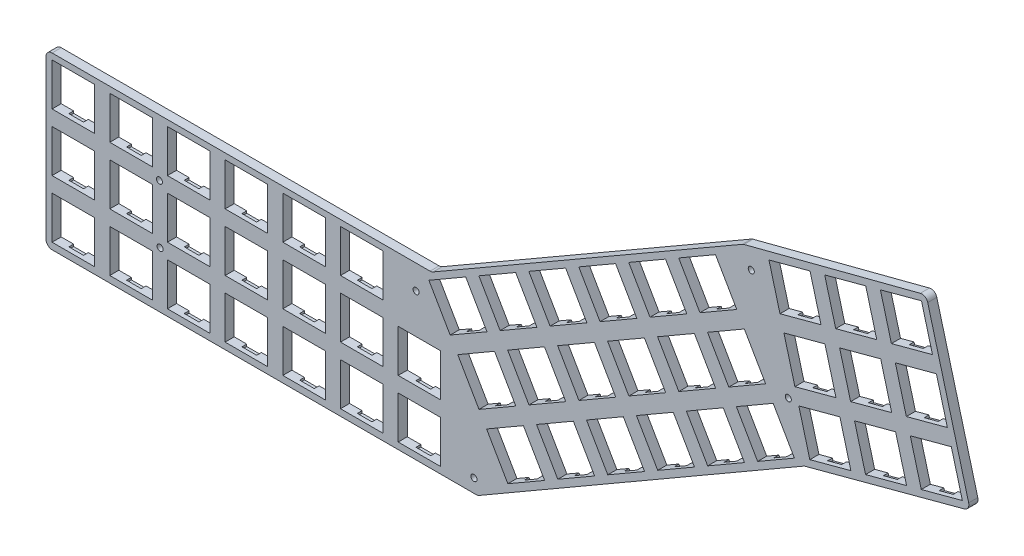
SolidWorks part; units mm, degrees
ref_plane "Plan de face" through (0, 0, 0) normal (0, 0, 1) x (1, 0, 0)
ref_plane "Plan de dessus" through (0, 0, 0) normal (0, 1, 0) x (1, 0, 0)
ref_plane "Plan de droite" through (0, 0, 0) normal (1, 0, 0) x (0, 0, -1)
sketch "Model" plane through (0, 0, 0) normal (0, 0, 1) x (1, 0, 0)
  line L0 (-149.6088, -15.6876) -> (-135.6088, -15.6876) construction
  line L1 (-149.6088, 3.3124) -> (-135.6088, 3.3124) construction
  line L2 (-149.6088, 3.3124) -> (-149.6088, -10.6876) construction
  line L3 (-149.6088, -10.6876) -> (-135.6088, -10.6876) construction
  line L4 (-135.6088, 3.3124) -> (-135.6088, -10.6876) construction
  line L5 (-149.6088, -15.6876) -> (-149.6088, -29.6876) construction
  line L6 (-149.6088, -29.6876) -> (-135.6088, -29.6876) construction
  line L7 (-135.6088, -15.6876) -> (-135.6088, -29.6876) construction
  line L8 (-149.6088, -34.6876) -> (-135.6088, -34.6876) construction
  line L9 (-149.6088, -34.6876) -> (-149.6088, -48.6876) construction
  line L10 (-149.6088, -48.6876) -> (-135.6088, -48.6876) construction
  line L11 (-135.6088, -34.6876) -> (-135.6088, -48.6876) construction
  line L12 (-149.6088, 3.3124) -> (-149.6088, -15.6876) construction
  line L13 (-130.6088, -15.6876) -> (-116.6088, -15.6876) construction
  line L14 (-130.6088, 3.3124) -> (-116.6088, 3.3124) construction
  line L15 (-130.6088, 3.3124) -> (-130.6088, -10.6876) construction
  line L16 (-130.6088, -10.6876) -> (-116.6088, -10.6876) construction
  line L17 (-116.6088, 3.3124) -> (-116.6088, -10.6876) construction
  line L18 (-130.6088, -15.6876) -> (-130.6088, -29.6876) construction
  line L19 (-130.6088, -29.6876) -> (-116.6088, -29.6876) construction
  line L20 (-116.6088, -15.6876) -> (-116.6088, -29.6876) construction
  line L21 (-130.6088, -34.6876) -> (-116.6088, -34.6876) construction
  line L22 (-130.6088, -34.6876) -> (-130.6088, -48.6876) construction
  line L23 (-130.6088, -48.6876) -> (-116.6088, -48.6876) construction
  line L24 (-116.6088, -34.6876) -> (-116.6088, -48.6876) construction
  line L25 (-130.6088, 3.3124) -> (-130.6088, -15.6876) construction
  line L26 (-111.6088, -15.6876) -> (-97.6088, -15.6876) construction
  line L27 (-111.6088, 3.3124) -> (-97.6088, 3.3124) construction
  line L28 (-111.6088, 3.3124) -> (-111.6088, -10.6876) construction
  line L29 (-111.6088, -10.6876) -> (-97.6088, -10.6876) construction
  line L30 (-97.6088, 3.3124) -> (-97.6088, -10.6876) construction
  line L31 (-111.6088, -15.6876) -> (-111.6088, -29.6876) construction
  line L32 (-111.6088, -29.6876) -> (-97.6088, -29.6876) construction
  line L33 (-97.6088, -15.6876) -> (-97.6088, -29.6876) construction
  line L34 (-111.6088, -34.6876) -> (-97.6088, -34.6876) construction
  line L35 (-111.6088, -34.6876) -> (-111.6088, -48.6876) construction
  line L36 (-111.6088, -48.6876) -> (-97.6088, -48.6876) construction
  line L37 (-97.6088, -34.6876) -> (-97.6088, -48.6876) construction
  line L38 (-111.6088, 3.3124) -> (-111.6088, -15.6876) construction
  line L39 (-92.6088, -15.6876) -> (-78.6088, -15.6876) construction
  line L40 (-92.6088, 3.3124) -> (-78.6088, 3.3124) construction
  line L41 (-92.6088, 3.3124) -> (-92.6088, -10.6876) construction
  line L42 (-92.6088, -10.6876) -> (-78.6088, -10.6876) construction
  line L43 (-78.6088, 3.3124) -> (-78.6088, -10.6876) construction
  line L44 (-92.6088, -15.6876) -> (-92.6088, -29.6876) construction
  line L45 (-92.6088, -29.6876) -> (-78.6088, -29.6876) construction
  line L46 (-78.6088, -15.6876) -> (-78.6088, -29.6876) construction
  line L47 (-92.6088, -34.6876) -> (-78.6088, -34.6876) construction
  line L48 (-92.6088, -34.6876) -> (-92.6088, -48.6876) construction
  line L49 (-92.6088, -48.6876) -> (-78.6088, -48.6876) construction
  line L50 (-78.6088, -34.6876) -> (-78.6088, -48.6876) construction
  line L51 (-92.6088, 3.3124) -> (-92.6088, -15.6876) construction
  line L52 (-73.6088, -15.6876) -> (-59.6088, -15.6876) construction
  line L53 (-73.6088, 3.3124) -> (-59.6088, 3.3124) construction
  line L54 (-73.6088, 3.3124) -> (-73.6088, -10.6876) construction
  line L55 (-73.6088, -10.6876) -> (-59.6088, -10.6876) construction
  line L56 (-59.6088, 3.3124) -> (-59.6088, -10.6876) construction
  line L57 (-73.6088, -15.6876) -> (-73.6088, -29.6876) construction
  line L58 (-73.6088, -29.6876) -> (-59.6088, -29.6876) construction
  line L59 (-59.6088, -15.6876) -> (-59.6088, -29.6876) construction
  line L60 (-73.6088, -34.6876) -> (-59.6088, -34.6876) construction
  line L61 (-73.6088, -34.6876) -> (-73.6088, -48.6876) construction
  line L62 (-73.6088, -48.6876) -> (-59.6088, -48.6876) construction
  line L63 (-59.6088, -34.6876) -> (-59.6088, -48.6876) construction
  line L64 (-73.6088, 3.3124) -> (-73.6088, -15.6876) construction
  line L65 (-54.6088, -15.6876) -> (-40.6088, -15.6876) construction
  line L66 (-54.6088, 3.3124) -> (-40.6088, 3.3124) construction
  line L67 (-54.6088, 3.3124) -> (-54.6088, -10.6876) construction
  line L68 (-54.6088, -10.6876) -> (-40.6088, -10.6876) construction
  line L69 (-40.6088, 3.3124) -> (-40.6088, -10.6876) construction
  line L70 (-54.6088, -15.6876) -> (-54.6088, -29.6876) construction
  line L71 (-54.6088, -29.6876) -> (-40.6088, -29.6876) construction
  line L72 (-40.6088, -15.6876) -> (-40.6088, -29.6876) construction
  line L73 (-54.6088, -34.6876) -> (-40.6088, -34.6876) construction
  line L74 (-54.6088, -34.6876) -> (-54.6088, -48.6876) construction
  line L75 (-54.6088, -48.6876) -> (-40.6088, -48.6876) construction
  line L76 (-40.6088, -34.6876) -> (-40.6088, -48.6876) construction
  line L77 (-54.6088, 3.3124) -> (-54.6088, -15.6876) construction
  line L78 (-35.6088, -15.6876) -> (-21.6088, -15.6876) construction
  line L79 (-35.6088, 3.3124) -> (-21.6088, 3.3124) construction
  line L80 (-35.6088, 3.3124) -> (-35.6088, -10.6876) construction
  line L81 (-35.6088, -10.6876) -> (-21.6088, -10.6876) construction
  line L82 (-21.6088, 3.3124) -> (-21.6088, -10.6876) construction
  line L83 (-35.6088, -15.6876) -> (-35.6088, -29.6876) construction
  line L84 (-35.6088, -29.6876) -> (-21.6088, -29.6876) construction
  line L85 (-21.6088, -15.6876) -> (-21.6088, -29.6876) construction
  line L86 (-35.6088, -34.6876) -> (-21.6088, -34.6876) construction
  line L87 (-35.6088, -34.6876) -> (-35.6088, -48.6876) construction
  line L88 (-35.6088, -48.6876) -> (-21.6088, -48.6876) construction
  line L89 (-21.6088, -34.6876) -> (-21.6088, -48.6876) construction
  line L90 (-35.6088, 3.3124) -> (-35.6088, -15.6876) construction
  line L91 (-149.6088, -15.6876) -> (-130.6088, -15.6876) construction
  line L92 (-19.6088, -13.6876) -> (-18.8669, -14.9725) construction
  line L93 (-37.6088, 5.3124) -> (-19.6088, 5.3124) construction
  line L94 (-19.6088, 5.3124) -> (-19.6088, -12.6876) construction
  line L95 (-37.6088, -12.6876) -> (-19.6088, -12.6876) construction
  line L96 (-37.6088, 5.3124) -> (-37.6088, -12.6876) construction
  line L97 (-56.6088, 5.3124) -> (-38.6088, 5.3124) construction
  line L98 (-38.6088, 5.3124) -> (-38.6088, -12.6876) construction
  line L99 (-56.6088, -12.6876) -> (-38.6088, -12.6876) construction
  line L100 (-56.6088, 5.3124) -> (-56.6088, -12.6876) construction
  line L101 (3.8161, 21.7392) -> (12.8161, 6.1508) construction
  line L102 (12.8161, 6.1508) -> (-2.7723, -2.8492) construction
  line L103 (-11.7723, 12.7392) -> (-2.7723, -2.8492) construction
  line L104 (3.8161, 21.7392) -> (-11.7723, 12.7392) construction
  line L105 (-12.6383, 12.2392) -> (-3.6383, -3.3492) construction
  line L106 (-3.6383, -3.3492) -> (-19.2268, -12.3492) construction
  line L107 (-28.2268, 3.2392) -> (-19.2268, -12.3492) construction
  line L108 (-12.6383, 12.2392) -> (-28.2268, 3.2392) construction
  line L109 (88.6341, 26.8303) -> (73.0456, 17.8303) construction
  line L110 (-13.3704, 9.5072) -> (-3.8704, -6.9473) construction
  line L111 (3.0841, 19.0072) -> (12.5841, 2.5527) construction
  line L112 (19.5386, 28.5072) -> (29.0386, 12.0527) construction
  line L113 (35.9931, 38.0072) -> (45.4931, 21.5527) construction
  line L114 (52.4475, 47.5072) -> (61.9475, 31.0527) construction
  line L115 (68.902, 57.0072) -> (78.402, 40.5527) construction
  line L116 (73.0456, 17.8303) -> (82.0456, 2.2418) construction
  line L117 (-6.4947, -30.4018) -> (0.5053, -42.5261) construction
  line L118 (12.6296, -35.5261) -> (0.5053, -42.5261) construction
  line L119 (5.6296, -23.4018) -> (12.6296, -35.5261) construction
  line L120 (5.6296, -23.4018) -> (-6.4947, -30.4018) construction
  line L121 (-15.9947, -13.9473) -> (-8.9947, -26.0717) construction
  line L122 (3.1296, -19.0717) -> (-8.9947, -26.0717) construction
  line L123 (-3.8704, -6.9473) -> (3.1296, -19.0717) construction
  line L124 (-25.4947, 2.5072) -> (-18.4947, -9.6172) construction
  line L125 (-6.3704, -2.6172) -> (-18.4947, -9.6172) construction
  line L126 (-13.3704, 9.5072) -> (-6.3704, -2.6172) construction
  line L127 (-13.3704, 9.5072) -> (-25.4947, 2.5072) construction
  line L128 (-3.8704, -6.9473) -> (-15.9947, -13.9473) construction
  line L129 (9.9597, -20.9018) -> (16.9597, -33.0261) construction
  line L130 (29.0841, -26.0261) -> (16.9597, -33.0261) construction
  line L131 (22.0841, -13.9018) -> (29.0841, -26.0261) construction
  line L132 (22.0841, -13.9018) -> (9.9597, -20.9018) construction
  line L133 (0.4597, -4.4473) -> (7.4597, -16.5717) construction
  line L134 (19.5841, -9.5717) -> (7.4597, -16.5717) construction
  line L135 (12.5841, 2.5527) -> (19.5841, -9.5717) construction
  line L136 (-9.0403, 12.0072) -> (-2.0403, -0.1172) construction
  line L137 (10.0841, 6.8828) -> (-2.0403, -0.1172) construction
  line L138 (3.0841, 19.0072) -> (10.0841, 6.8828) construction
  line L139 (3.0841, 19.0072) -> (-9.0403, 12.0072) construction
  line L140 (12.5841, 2.5527) -> (0.4597, -4.4473) construction
  line L141 (26.4142, -11.4018) -> (33.4142, -23.5261) construction
  line L142 (45.5386, -16.5261) -> (33.4142, -23.5261) construction
  line L143 (38.5386, -4.4018) -> (45.5386, -16.5261) construction
  line L144 (38.5386, -4.4018) -> (26.4142, -11.4018) construction
  line L145 (16.9142, 5.0527) -> (23.9142, -7.0717) construction
  line L146 (36.0386, -0.0717) -> (23.9142, -7.0717) construction
  line L147 (29.0386, 12.0527) -> (36.0386, -0.0717) construction
  line L148 (7.4142, 21.5072) -> (14.4142, 9.3828) construction
  line L149 (26.5386, 16.3828) -> (14.4142, 9.3828) construction
  line L150 (19.5386, 28.5072) -> (26.5386, 16.3828) construction
  line L151 (19.5386, 28.5072) -> (7.4142, 21.5072) construction
  line L152 (29.0386, 12.0527) -> (16.9142, 5.0527) construction
  line L153 (42.8687, -1.9018) -> (49.8687, -14.0261) construction
  line L154 (61.9931, -7.0261) -> (49.8687, -14.0261) construction
  line L155 (54.9931, 5.0982) -> (61.9931, -7.0261) construction
  line L156 (54.9931, 5.0982) -> (42.8687, -1.9018) construction
  line L157 (33.3687, 14.5527) -> (40.3687, 2.4283) construction
  line L158 (52.4931, 9.4283) -> (40.3687, 2.4283) construction
  line L159 (45.4931, 21.5527) -> (52.4931, 9.4283) construction
  line L160 (23.8687, 31.0072) -> (30.8687, 18.8828) construction
  line L161 (42.9931, 25.8828) -> (30.8687, 18.8828) construction
  line L162 (35.9931, 38.0072) -> (42.9931, 25.8828) construction
  line L163 (35.9931, 38.0072) -> (23.8687, 31.0072) construction
  line L164 (45.4931, 21.5527) -> (33.3687, 14.5527) construction
  line L165 (59.3232, 7.5982) -> (66.3232, -4.5261) construction
  line L166 (78.4475, 2.4739) -> (66.3232, -4.5261) construction
  line L167 (71.4475, 14.5982) -> (78.4475, 2.4739) construction
  line L168 (71.4475, 14.5982) -> (59.3232, 7.5982) construction
  line L169 (49.8232, 24.0527) -> (56.8232, 11.9283) construction
  line L170 (68.9475, 18.9283) -> (56.8232, 11.9283) construction
  line L171 (61.9475, 31.0527) -> (68.9475, 18.9283) construction
  line L172 (40.3232, 40.5072) -> (47.3232, 28.3828) construction
  line L173 (59.4475, 35.3828) -> (47.3232, 28.3828) construction
  line L174 (52.4475, 47.5072) -> (59.4475, 35.3828) construction
  line L175 (52.4475, 47.5072) -> (40.3232, 40.5072) construction
  line L176 (61.9475, 31.0527) -> (49.8232, 24.0527) construction
  line L177 (75.7777, 17.0982) -> (82.7777, 4.9739) construction
  line L178 (94.902, 11.9739) -> (82.7777, 4.9739) construction
  line L179 (87.902, 24.0982) -> (94.902, 11.9739) construction
  line L180 (87.902, 24.0982) -> (75.7777, 17.0982) construction
  line L181 (66.2777, 33.5527) -> (73.2777, 21.4283) construction
  line L182 (85.402, 28.4283) -> (73.2777, 21.4283) construction
  line L183 (78.402, 40.5527) -> (85.402, 28.4283) construction
  line L184 (56.7777, 50.0072) -> (63.7777, 37.8828) construction
  line L185 (75.902, 44.8828) -> (63.7777, 37.8828) construction
  line L186 (68.902, 57.0072) -> (75.902, 44.8828) construction
  line L187 (68.902, 57.0072) -> (56.7777, 50.0072) construction
  line L188 (78.402, 40.5527) -> (66.2777, 33.5527) construction
  line L189 (97.6341, 11.2418) -> (82.0456, 2.2418) construction
  line L190 (88.6341, 26.8303) -> (97.6341, 11.2418) construction
  line L191 (102.6968, 0.3259) -> (93.4333, 22.69) construction
  line L192 (93.8992, 29.0112) -> (98.558, 11.6245) construction
  line L193 (98.558, 11.6245) -> (115.9446, 16.2832) construction
  line L194 (111.2859, 33.6699) -> (115.9446, 16.2832) construction
  line L195 (86.5136, 64.3021) -> (91.4311, 45.9495) construction
  line L196 (93.8992, 29.0112) -> (111.2859, 33.6699) construction
  line L197 (91.4311, 45.9495) -> (104.9541, 49.573) construction
  line L198 (86.5136, 64.3021) -> (100.0365, 67.9256) construction
  line L199 (86.5136, 64.3021) -> (90.137, 50.7792) construction
  line L200 (90.137, 50.7792) -> (103.66, 54.4026) construction
  line L201 (100.0365, 67.9256) -> (103.66, 54.4026) construction
  line L202 (91.4311, 45.9495) -> (95.0546, 32.4266) construction
  line L203 (95.0546, 32.4266) -> (108.5776, 36.05) construction
  line L204 (104.9541, 49.573) -> (108.5776, 36.05) construction
  line L205 (96.3487, 27.5969) -> (109.8717, 31.2204) construction
  line L206 (96.3487, 27.5969) -> (99.9722, 14.074) construction
  line L207 (99.9722, 14.074) -> (113.4951, 17.6974) construction
  line L208 (109.8717, 31.2204) -> (113.4951, 17.6974) construction
  line L209 (109.7837, 50.8671) -> (123.3067, 54.4906) construction
  line L210 (104.8662, 69.2197) -> (118.3891, 72.8432) construction
  line L211 (104.8662, 69.2197) -> (108.4896, 55.6967) construction
  line L212 (108.4896, 55.6967) -> (122.0126, 59.3202) construction
  line L213 (118.3891, 72.8432) -> (122.0126, 59.3202) construction
  line L214 (109.7837, 50.8671) -> (113.4072, 37.3441) construction
  line L215 (113.4072, 37.3441) -> (126.9302, 40.9676) construction
  line L216 (123.3067, 54.4906) -> (126.9302, 40.9676) construction
  line L217 (114.7013, 32.5145) -> (128.2243, 36.138) construction
  line L218 (114.7013, 32.5145) -> (118.3248, 18.9915) construction
  line L219 (118.3248, 18.9915) -> (131.8477, 22.615) construction
  line L220 (128.2243, 36.138) -> (131.8477, 22.615) construction
  line L221 (112.2518, 33.9287) -> (116.9105, 16.5421) construction
  line L222 (116.9105, 16.5421) -> (134.2972, 21.2008) construction
  line L223 (129.6385, 38.5875) -> (134.2972, 21.2008) construction
  line L224 (104.8662, 69.2197) -> (109.7837, 50.8671) construction
  line L225 (112.2518, 33.9287) -> (129.6385, 38.5875) construction
  line L226 (128.1363, 55.7847) -> (141.6593, 59.4081) construction
  line L227 (123.2188, 74.1372) -> (136.7417, 77.7607) construction
  line L228 (123.2188, 74.1372) -> (126.8422, 60.6143) construction
  line L229 (126.8422, 60.6143) -> (140.3652, 64.2378) construction
  line L230 (136.7417, 77.7607) -> (140.3652, 64.2378) construction
  line L231 (128.1363, 55.7847) -> (131.7598, 42.2617) construction
  line L232 (131.7598, 42.2617) -> (145.2828, 45.8852) construction
  line L233 (141.6593, 59.4081) -> (145.2828, 45.8852) construction
  line L234 (133.0539, 37.4321) -> (146.5768, 41.0555) construction
  line L235 (133.0539, 37.4321) -> (136.6774, 23.9091) construction
  line L236 (136.6774, 23.9091) -> (150.2003, 27.5326) construction
  line L237 (146.5768, 41.0555) -> (150.2003, 27.5326) construction
  line L238 (130.6044, 38.8463) -> (135.2631, 21.4596) construction
  line L239 (135.2631, 21.4596) -> (152.6498, 26.1184) construction
  line L240 (147.9911, 43.505) -> (152.6498, 26.1184) construction
  line L241 (123.2188, 74.1372) -> (128.1363, 55.7847) construction
  line L242 (130.6044, 38.8463) -> (147.9911, 43.505) construction
  line L243 (91.4311, 45.9495) -> (109.7837, 50.8671) construction
  line L244 (-37.6088, -13.6876) -> (-19.6088, -13.6876) construction
  line L245 (-19.6088, -13.6876) -> (-19.6088, -31.6876) construction
  line L246 (-37.6088, -31.6876) -> (-19.6088, -31.6876) construction
  line L247 (-37.6088, -13.6876) -> (-37.6088, -31.6876) construction
  line L248 (-3.1383, -4.2153) -> (-18.7268, -13.2153) construction
  line L249 (-18.7268, -13.2153) -> (-9.7268, -28.8037) construction
  line L250 (5.8617, -19.8037) -> (-9.7268, -28.8037) construction
  line L251 (-3.1383, -4.2153) -> (5.8617, -19.8037) construction
  line L252 (-18.7268, -13.2153) -> (-18.009, -14.4585) construction
  line L253 (88.9817, 47.3637) -> (93.6404, 29.9771) construction
  line L254 (93.6404, 29.9771) -> (111.0271, 34.6358) construction
  line L255 (106.3683, 52.0225) -> (111.0271, 34.6358) construction
  line L256 (88.9817, 47.3637) -> (106.3683, 52.0225) construction
  line L257 (79.1341, 43.2847) -> (88.1341, 27.6963) construction
  line L258 (88.1341, 27.6963) -> (72.5456, 18.6963) construction
  line L259 (63.5456, 34.2847) -> (72.5456, 18.6963) construction
  line L260 (79.1341, 43.2847) -> (63.5456, 34.2847) construction
  line L261 (120.7693, 75.5515) -> (138.1559, 80.2102) construction
  line L262 (-170.3739, 2.0225) -> (-152.3739, 2.0225) construction
  line L263 (-170.3739, 2.0225) -> (-170.3739, -30.9775) construction
  line L264 (-170.3739, -30.9775) -> (-152.3739, -30.9775) construction
  line L265 (-152.3739, 2.0225) -> (-152.3739, -30.9775) construction
  line L266 (138.1559, 80.2102) -> (142.8147, 62.8235) construction
  line L267 (125.428, 58.1648) -> (142.8147, 62.8235) construction
  line L268 (120.7693, 75.5515) -> (125.428, 58.1648) construction
  line L269 (-151.6088, -50.6876) -> (-133.6088, -50.6876) construction
  line L270 (-133.6088, -32.6876) -> (-133.6088, -50.6876) construction
  line L271 (-151.6088, -32.6876) -> (-133.6088, -32.6876) construction
  line L272 (-151.6088, -32.6876) -> (-151.6088, -50.6876) construction
  line L273 (-37.6088, -50.6876) -> (-19.6088, -50.6876) construction
  line L274 (-19.6088, -32.6876) -> (-19.6088, -50.6876) construction
  line L275 (-37.6088, -32.6876) -> (-19.6088, -32.6876) construction
  line L276 (-37.6088, -32.6876) -> (-37.6088, -50.6876) construction
  line L277 (-151.6088, 5.3124) -> (-133.6088, 5.3124) construction
  line L278 (-133.6088, 5.3124) -> (-133.6088, -12.6876) construction
  line L279 (-151.6088, -12.6876) -> (-133.6088, -12.6876) construction
  line L280 (-151.6088, 5.3124) -> (-151.6088, -12.6876) construction
  line L281 (69.6341, 59.7392) -> (54.0456, 50.7392) construction
  line L282 (54.0456, 50.7392) -> (63.0456, 35.1508) construction
  line L283 (78.6341, 44.1508) -> (63.0456, 35.1508) construction
  line L284 (69.6341, 59.7392) -> (78.6341, 44.1508) construction
  line L285 (-172.3739, 5.3124) -> (-24.636, 5.3124)
  line L286 (-24.636, 5.3124) -> (77.9848, 64.5605)
  line L287 (138.1559, 80.2102) -> (77.9848, 64.5605)
  line L288 (138.1559, 80.2102) -> (152.6498, 26.1184)
  line L289 (152.6498, 26.1184) -> (98.065, 11.5079)
  line L290 (98.065, 11.5079) -> (82.0456, 2.2418)
  line L291 (82.0456, 2.2418) -> (-9.4597, -50.6876)
  line L292 (-37.6088, -50.6876) -> (-19.6088, -50.6876)
  line L293 (-19.6088, -50.6876) -> (-9.4597, -50.6876)
  line L294 (-172.3739, 5.3124) -> (-172.3739, -50.6876)
  line L295 (-172.3739, -50.6876) -> (-37.6088, -50.6876)
  line L296 (101.9307, 2.1754) -> (100.0173, 6.7948) construction
  line L297 (-152.3739, 2.0225) -> (-172.3739, 2.0225) construction
  line L298 (-152.3739, 5.3124) -> (-172.3739, 5.3124) construction
  line L299 (-152.3739, 5.3124) -> (-152.3739, -32.6876) construction
  line L300 (-152.3739, -32.6876) -> (-172.3739, -32.6876) construction
  line L301 (-172.3739, 5.3124) -> (-172.3739, -32.6876) construction
  circle A0 centre (100.0173, 6.7948) radius 1.5 construction
sketch "Esquisse2" plane through (0, 0, 0) normal (0, 0, 1) x (1, 0, 0)
  line L0 (152.8114, 25.9717) -> (138.2826, 80.2215)
  line L1 (98.1506, 11.3316) -> (152.8114, 25.9717)
  line L2 (-9.3986, -50.8585) -> (98.1506, 11.3316)
  line L3 (-151.6088, -50.8585) -> (-9.3986, -50.8585)
  line L5 (-24.5886, 5.3017) -> (-151.6088, 5.2929)
  line L6 (78.0109, 64.5416) -> (-24.5886, 5.3017)
  line L7 (138.2826, 80.2215) -> (78.0109, 64.5416)
  line L40 (-151.6088, 5.3124) -> (-151.6088, -50.8585)
  line L41 (-54.6088, -34.6876) -> (-54.6088, -48.6876) construction
  line L42 (-54.6088, -48.6876) -> (-40.6088, -48.6876) construction
  line L43 (-40.6088, -34.6876) -> (-40.6088, -48.6876) construction
  line L44 (-54.6088, -34.6876) -> (-40.6088, -34.6876) construction
  line L45 (-35.6088, -34.6876) -> (-35.6088, -48.6876) construction
  line L46 (-35.6088, -48.6876) -> (-21.6088, -48.6876) construction
  line L47 (-21.6088, -34.6876) -> (-21.6088, -48.6876) construction
  line L48 (-35.6088, -34.6876) -> (-21.6088, -34.6876) construction
  line L49 (-35.6088, -15.6876) -> (-35.6088, -29.6876) construction
  line L50 (-35.6088, -29.6876) -> (-21.6088, -29.6876) construction
  line L51 (-21.6088, -15.6876) -> (-21.6088, -29.6876) construction
  line L52 (-35.6088, -15.6876) -> (-21.6088, -15.6876) construction
  line L53 (-54.6088, -15.6876) -> (-54.6088, -29.6876) construction
  line L54 (-54.6088, -29.6876) -> (-40.6088, -29.6876) construction
  line L55 (-40.6088, -15.6876) -> (-40.6088, -29.6876) construction
  line L56 (-54.6088, -15.6876) -> (-40.6088, -15.6876) construction
  line L57 (-54.6088, 3.3124) -> (-54.6088, -10.6876) construction
  line L58 (-54.6088, -10.6876) -> (-40.6088, -10.6876) construction
  line L59 (-40.6088, 3.3124) -> (-40.6088, -10.6876) construction
  line L60 (-54.6088, 3.3124) -> (-40.6088, 3.3124) construction
  line L61 (-73.6088, -34.6876) -> (-73.6088, -48.6876) construction
  line L62 (-73.6088, -48.6876) -> (-59.6088, -48.6876) construction
  line L63 (-59.6088, -34.6876) -> (-59.6088, -48.6876) construction
  line L64 (-73.6088, -34.6876) -> (-59.6088, -34.6876) construction
  line L65 (-73.6088, -15.6876) -> (-73.6088, -29.6876) construction
  line L66 (-73.6088, -29.6876) -> (-59.6088, -29.6876) construction
  line L67 (-59.6088, -15.6876) -> (-59.6088, -29.6876) construction
  line L68 (-73.6088, -15.6876) -> (-59.6088, -15.6876) construction
  line L69 (-73.6088, 3.3124) -> (-73.6088, -10.6876) construction
  line L70 (-73.6088, -10.6876) -> (-59.6088, -10.6876) construction
  line L71 (-59.6088, 3.3124) -> (-59.6088, -10.6876) construction
  line L72 (-73.6088, 3.3124) -> (-59.6088, 3.3124) construction
  line L73 (-92.6088, -34.6876) -> (-92.6088, -48.6876) construction
  line L74 (-92.6088, -48.6876) -> (-78.6088, -48.6876) construction
  line L75 (-78.6088, -34.6876) -> (-78.6088, -48.6876) construction
  line L76 (-92.6088, -34.6876) -> (-78.6088, -34.6876) construction
  line L77 (-92.6088, -15.6876) -> (-92.6088, -29.6876) construction
  line L78 (-92.6088, -29.6876) -> (-78.6088, -29.6876) construction
  line L79 (-78.6088, -15.6876) -> (-78.6088, -29.6876) construction
  line L80 (-92.6088, -15.6876) -> (-78.6088, -15.6876) construction
  line L81 (-92.6088, 3.3124) -> (-92.6088, -10.6876) construction
  line L82 (-92.6088, -10.6876) -> (-78.6088, -10.6876) construction
  line L83 (-78.6088, 3.3124) -> (-78.6088, -10.6876) construction
  line L84 (-92.6088, 3.3124) -> (-78.6088, 3.3124) construction
  line L85 (-111.6088, -34.6876) -> (-111.6088, -48.6876) construction
  line L86 (-111.6088, -48.6876) -> (-97.6088, -48.6876) construction
  line L87 (-97.6088, -34.6876) -> (-97.6088, -48.6876) construction
  line L88 (-111.6088, -34.6876) -> (-97.6088, -34.6876) construction
  line L89 (-111.6088, -15.6876) -> (-111.6088, -29.6876) construction
  line L90 (-111.6088, -29.6876) -> (-97.6088, -29.6876) construction
  line L91 (-97.6088, -15.6876) -> (-97.6088, -29.6876) construction
  line L92 (-111.6088, -15.6876) -> (-97.6088, -15.6876) construction
  line L93 (-130.6088, -34.6876) -> (-130.6088, -48.6876) construction
  line L94 (-130.6088, -48.6876) -> (-116.6088, -48.6876) construction
  line L95 (-116.6088, -34.6876) -> (-116.6088, -48.6876) construction
  line L96 (-130.6088, -34.6876) -> (-116.6088, -34.6876) construction
  line L97 (-130.6088, -15.6876) -> (-130.6088, -29.6876) construction
  line L98 (-130.6088, -29.6876) -> (-116.6088, -29.6876) construction
  line L99 (-116.6088, -15.6876) -> (-116.6088, -29.6876) construction
  line L100 (-130.6088, -15.6876) -> (-116.6088, -15.6876) construction
  line L101 (-149.6088, -34.6876) -> (-149.6088, -48.6876) construction
  line L102 (-149.6088, -48.6876) -> (-135.6088, -48.6876) construction
  line L103 (-135.6088, -34.6876) -> (-135.6088, -48.6876) construction
  line L104 (-149.6088, -34.6876) -> (-135.6088, -34.6876) construction
  line L105 (-149.6088, -15.6876) -> (-149.6088, -29.6876) construction
  line L106 (-149.6088, -29.6876) -> (-135.6088, -29.6876) construction
  line L107 (-135.6088, -15.6876) -> (-135.6088, -29.6876) construction
  line L108 (-149.6088, -15.6876) -> (-135.6088, -15.6876) construction
  line L109 (-111.6088, 3.3124) -> (-111.6088, -10.6876) construction
  line L110 (-111.6088, -10.6876) -> (-97.6088, -10.6876) construction
  line L111 (-97.6088, 3.3124) -> (-97.6088, -10.6876) construction
  line L112 (-111.6088, 3.3124) -> (-97.6088, 3.3124) construction
  line L113 (-130.6088, 3.3124) -> (-130.6088, -10.6876) construction
  line L114 (-130.6088, -10.6876) -> (-116.6088, -10.6876) construction
  line L115 (-116.6088, 3.3124) -> (-116.6088, -10.6876) construction
  line L116 (-130.6088, 3.3124) -> (-116.6088, 3.3124) construction
  line L117 (-149.6088, 3.3124) -> (-149.6088, -10.6876) construction
  line L118 (-149.6088, -10.6876) -> (-135.6088, -10.6876) construction
  line L119 (-135.6088, 3.3124) -> (-135.6088, -10.6876) construction
  line L120 (-149.6088, 3.3124) -> (-135.6088, 3.3124) construction
  line L121 (-54.6088, -34.6876) -> (-54.6088, -48.6876)
  line L122 (-54.6088, -48.6876) -> (-40.6088, -48.6876)
  line L123 (-40.6088, -34.6876) -> (-40.6088, -48.6876)
  line L124 (-54.6088, -34.6876) -> (-40.6088, -34.6876)
  line L125 (-35.6088, -34.6876) -> (-35.6088, -48.6876)
  line L126 (-35.6088, -48.6876) -> (-21.6088, -48.6876)
  line L127 (-21.6088, -34.6876) -> (-21.6088, -48.6876)
  line L128 (-35.6088, -34.6876) -> (-21.6088, -34.6876)
  line L129 (-35.6088, -15.6876) -> (-35.6088, -29.6876)
  line L130 (-35.6088, -29.6876) -> (-21.6088, -29.6876)
  line L131 (-21.6088, -15.6876) -> (-21.6088, -29.6876)
  line L132 (-35.6088, -15.6876) -> (-21.6088, -15.6876)
  line L133 (-54.6088, -15.6876) -> (-54.6088, -29.6876)
  line L134 (-54.6088, -29.6876) -> (-40.6088, -29.6876)
  line L135 (-40.6088, -15.6876) -> (-40.6088, -29.6876)
  line L136 (-54.6088, -15.6876) -> (-40.6088, -15.6876)
  line L137 (-54.6088, 3.3124) -> (-54.6088, -10.6876)
  line L138 (-54.6088, -10.6876) -> (-40.6088, -10.6876)
  line L139 (-40.6088, 3.3124) -> (-40.6088, -10.6876)
  line L140 (-54.6088, 3.3124) -> (-40.6088, 3.3124)
  line L141 (-73.6088, -34.6876) -> (-73.6088, -48.6876)
  line L142 (-73.6088, -48.6876) -> (-59.6088, -48.6876)
  line L143 (-59.6088, -34.6876) -> (-59.6088, -48.6876)
  line L144 (-73.6088, -34.6876) -> (-59.6088, -34.6876)
  line L145 (-73.6088, -15.6876) -> (-73.6088, -29.6876)
  line L146 (-73.6088, -29.6876) -> (-59.6088, -29.6876)
  line L147 (-59.6088, -15.6876) -> (-59.6088, -29.6876)
  line L148 (-73.6088, -15.6876) -> (-59.6088, -15.6876)
  line L149 (-73.6088, 3.3124) -> (-73.6088, -10.6876)
  line L150 (-73.6088, -10.6876) -> (-59.6088, -10.6876)
  line L151 (-59.6088, 3.3124) -> (-59.6088, -10.6876)
  line L152 (-73.6088, 3.3124) -> (-59.6088, 3.3124)
  line L153 (-92.6088, -34.6876) -> (-92.6088, -48.6876)
  line L154 (-92.6088, -48.6876) -> (-78.6088, -48.6876)
  line L155 (-78.6088, -34.6876) -> (-78.6088, -48.6876)
  line L156 (-92.6088, -34.6876) -> (-78.6088, -34.6876)
  line L157 (-92.6088, -15.6876) -> (-92.6088, -29.6876)
  line L158 (-92.6088, -29.6876) -> (-78.6088, -29.6876)
  line L159 (-78.6088, -15.6876) -> (-78.6088, -29.6876)
  line L160 (-92.6088, -15.6876) -> (-78.6088, -15.6876)
  line L161 (-92.6088, 3.3124) -> (-92.6088, -10.6876)
  line L162 (-92.6088, -10.6876) -> (-78.6088, -10.6876)
  line L163 (-78.6088, 3.3124) -> (-78.6088, -10.6876)
  line L164 (-92.6088, 3.3124) -> (-78.6088, 3.3124)
  line L165 (-111.6088, -34.6876) -> (-111.6088, -48.6876)
  line L166 (-111.6088, -48.6876) -> (-97.6088, -48.6876)
  line L167 (-97.6088, -34.6876) -> (-97.6088, -48.6876)
  line L168 (-111.6088, -34.6876) -> (-97.6088, -34.6876)
  line L169 (-111.6088, -15.6876) -> (-111.6088, -29.6876)
  line L170 (-111.6088, -29.6876) -> (-97.6088, -29.6876)
  line L171 (-97.6088, -15.6876) -> (-97.6088, -29.6876)
  line L172 (-111.6088, -15.6876) -> (-97.6088, -15.6876)
  line L173 (-130.6088, -34.6876) -> (-130.6088, -48.6876)
  line L174 (-130.6088, -48.6876) -> (-116.6088, -48.6876)
  line L175 (-116.6088, -34.6876) -> (-116.6088, -48.6876)
  line L176 (-130.6088, -34.6876) -> (-116.6088, -34.6876)
  line L177 (-130.6088, -15.6876) -> (-130.6088, -29.6876)
  line L178 (-130.6088, -29.6876) -> (-116.6088, -29.6876)
  line L179 (-116.6088, -15.6876) -> (-116.6088, -29.6876)
  line L180 (-130.6088, -15.6876) -> (-116.6088, -15.6876)
  line L181 (-149.6088, -34.6876) -> (-149.6088, -48.6876)
  line L182 (-149.6088, -48.6876) -> (-135.6088, -48.6876)
  line L183 (-135.6088, -34.6876) -> (-135.6088, -48.6876)
  line L184 (-149.6088, -34.6876) -> (-135.6088, -34.6876)
  line L185 (-149.6088, -15.6876) -> (-149.6088, -29.6876)
  line L186 (-149.6088, -29.6876) -> (-135.6088, -29.6876)
  line L187 (-135.6088, -15.6876) -> (-135.6088, -29.6876)
  line L188 (-149.6088, -15.6876) -> (-135.6088, -15.6876)
  line L189 (-111.6088, 3.3124) -> (-111.6088, -10.6876)
  line L190 (-111.6088, -10.6876) -> (-97.6088, -10.6876)
  line L191 (-97.6088, 3.3124) -> (-97.6088, -10.6876)
  line L192 (-111.6088, 3.3124) -> (-97.6088, 3.3124)
  line L193 (-130.6088, 3.3124) -> (-130.6088, -10.6876)
  line L194 (-130.6088, -10.6876) -> (-116.6088, -10.6876)
  line L195 (-116.6088, 3.3124) -> (-116.6088, -10.6876)
  line L196 (-130.6088, 3.3124) -> (-116.6088, 3.3124)
  line L197 (-149.6088, 3.3124) -> (-149.6088, -10.6876)
  line L198 (-149.6088, -10.6876) -> (-135.6088, -10.6876)
  line L199 (-135.6088, 3.3124) -> (-135.6088, -10.6876)
  line L200 (-149.6088, 3.3124) -> (-135.6088, 3.3124)
  line L201 (96.3487, 27.5969) -> (99.9722, 14.074) construction
  line L202 (99.9722, 14.074) -> (113.4951, 17.6974) construction
  line L203 (109.8717, 31.2204) -> (113.4951, 17.6974) construction
  line L204 (96.3487, 27.5969) -> (109.8717, 31.2204) construction
  line L205 (91.4311, 45.9495) -> (95.0546, 32.4266) construction
  line L206 (95.0546, 32.4266) -> (108.5776, 36.05) construction
  line L207 (104.9541, 49.573) -> (108.5776, 36.05) construction
  line L208 (91.4311, 45.9495) -> (104.9541, 49.573) construction
  line L209 (109.7837, 50.8671) -> (113.4072, 37.3441) construction
  line L210 (113.4072, 37.3441) -> (126.9302, 40.9676) construction
  line L211 (123.3067, 54.4906) -> (126.9302, 40.9676) construction
  line L212 (109.7837, 50.8671) -> (123.3067, 54.4906) construction
  line L213 (114.7013, 32.5145) -> (118.3248, 18.9915) construction
  line L214 (118.3248, 18.9915) -> (131.8477, 22.615) construction
  line L215 (128.2243, 36.138) -> (131.8477, 22.615) construction
  line L216 (114.7013, 32.5145) -> (128.2243, 36.138) construction
  line L217 (133.0539, 37.4321) -> (136.6774, 23.9091) construction
  line L218 (136.6774, 23.9091) -> (150.2003, 27.5326) construction
  line L219 (146.5768, 41.0555) -> (150.2003, 27.5326) construction
  line L220 (133.0539, 37.4321) -> (146.5768, 41.0555) construction
  line L221 (128.1363, 55.7847) -> (131.7598, 42.2617) construction
  line L222 (131.7598, 42.2617) -> (145.2828, 45.8852) construction
  line L223 (141.6593, 59.4081) -> (145.2828, 45.8852) construction
  line L224 (128.1363, 55.7847) -> (141.6593, 59.4081) construction
  line L225 (123.2188, 74.1372) -> (126.8422, 60.6143) construction
  line L226 (126.8422, 60.6143) -> (140.3652, 64.2378) construction
  line L227 (136.7417, 77.7607) -> (140.3652, 64.2378) construction
  line L228 (123.2188, 74.1372) -> (136.7417, 77.7607) construction
  line L229 (104.8662, 69.2197) -> (108.4896, 55.6967) construction
  line L230 (108.4896, 55.6967) -> (122.0126, 59.3202) construction
  line L231 (118.3891, 72.8432) -> (122.0126, 59.3202) construction
  line L232 (104.8662, 69.2197) -> (118.3891, 72.8432) construction
  line L233 (86.5136, 64.3021) -> (90.137, 50.7792) construction
  line L234 (90.137, 50.7792) -> (103.66, 54.4026) construction
  line L235 (100.0365, 67.9256) -> (103.66, 54.4026) construction
  line L236 (86.5136, 64.3021) -> (100.0365, 67.9256) construction
  line L237 (87.902, 24.0982) -> (94.902, 11.9739) construction
  line L238 (94.902, 11.9739) -> (82.7777, 4.9739) construction
  line L239 (75.7777, 17.0982) -> (82.7777, 4.9739) construction
  line L240 (87.902, 24.0982) -> (75.7777, 17.0982) construction
  line L241 (78.402, 40.5527) -> (85.402, 28.4283) construction
  line L242 (85.402, 28.4283) -> (73.2777, 21.4283) construction
  line L243 (66.2777, 33.5527) -> (73.2777, 21.4283) construction
  line L244 (78.402, 40.5527) -> (66.2777, 33.5527) construction
  line L245 (68.902, 57.0072) -> (75.902, 44.8828) construction
  line L246 (75.902, 44.8828) -> (63.7777, 37.8828) construction
  line L247 (56.7777, 50.0072) -> (63.7777, 37.8828) construction
  line L248 (68.902, 57.0072) -> (56.7777, 50.0072) construction
  line L249 (71.4475, 14.5982) -> (78.4475, 2.4739) construction
  line L250 (78.4475, 2.4739) -> (66.3232, -4.5261) construction
  line L251 (59.3232, 7.5982) -> (66.3232, -4.5261) construction
  line L252 (71.4475, 14.5982) -> (59.3232, 7.5982) construction
  line L253 (61.9475, 31.0527) -> (68.9475, 18.9283) construction
  line L254 (68.9475, 18.9283) -> (56.8232, 11.9283) construction
  line L255 (49.8232, 24.0527) -> (56.8232, 11.9283) construction
  line L256 (61.9475, 31.0527) -> (49.8232, 24.0527) construction
  line L257 (52.4475, 47.5072) -> (59.4475, 35.3828) construction
  line L258 (59.4475, 35.3828) -> (47.3232, 28.3828) construction
  line L259 (40.3232, 40.5072) -> (47.3232, 28.3828) construction
  line L260 (52.4475, 47.5072) -> (40.3232, 40.5072) construction
  line L261 (54.9931, 5.0982) -> (61.9931, -7.0261) construction
  line L262 (61.9931, -7.0261) -> (49.8687, -14.0261) construction
  line L263 (42.8687, -1.9018) -> (49.8687, -14.0261) construction
  line L264 (54.9931, 5.0982) -> (42.8687, -1.9018) construction
  line L265 (45.4931, 21.5527) -> (52.4931, 9.4283) construction
  line L266 (52.4931, 9.4283) -> (40.3687, 2.4283) construction
  line L267 (33.3687, 14.5527) -> (40.3687, 2.4283) construction
  line L268 (45.4931, 21.5527) -> (33.3687, 14.5527) construction
  line L269 (38.5386, -4.4018) -> (45.5386, -16.5261) construction
  line L270 (45.5386, -16.5261) -> (33.4142, -23.5261) construction
  line L271 (26.4142, -11.4018) -> (33.4142, -23.5261) construction
  line L272 (38.5386, -4.4018) -> (26.4142, -11.4018) construction
  line L273 (29.0386, 12.0527) -> (36.0386, -0.0717) construction
  line L274 (36.0386, -0.0717) -> (23.9142, -7.0717) construction
  line L275 (16.9142, 5.0527) -> (23.9142, -7.0717) construction
  line L276 (29.0386, 12.0527) -> (16.9142, 5.0527) construction
  line L277 (35.9931, 38.0072) -> (42.9931, 25.8828) construction
  line L278 (42.9931, 25.8828) -> (30.8687, 18.8828) construction
  line L279 (23.8687, 31.0072) -> (30.8687, 18.8828) construction
  line L280 (35.9931, 38.0072) -> (23.8687, 31.0072) construction
  line L281 (19.5386, 28.5072) -> (26.5386, 16.3828) construction
  line L282 (26.5386, 16.3828) -> (14.4142, 9.3828) construction
  line L283 (7.4142, 21.5072) -> (14.4142, 9.3828) construction
  line L284 (19.5386, 28.5072) -> (7.4142, 21.5072) construction
  line L285 (3.0841, 19.0072) -> (10.0841, 6.8828) construction
  line L286 (10.0841, 6.8828) -> (-2.0403, -0.1172) construction
  line L287 (-9.0403, 12.0072) -> (-2.0403, -0.1172) construction
  line L288 (3.0841, 19.0072) -> (-9.0403, 12.0072) construction
  line L289 (12.5841, 2.5527) -> (19.5841, -9.5717) construction
  line L290 (19.5841, -9.5717) -> (7.4597, -16.5717) construction
  line L291 (0.4597, -4.4473) -> (7.4597, -16.5717) construction
  line L292 (12.5841, 2.5527) -> (0.4597, -4.4473) construction
  line L293 (22.0841, -13.9018) -> (29.0841, -26.0261) construction
  line L294 (29.0841, -26.0261) -> (16.9597, -33.0261) construction
  line L295 (9.9597, -20.9018) -> (16.9597, -33.0261) construction
  line L296 (22.0841, -13.9018) -> (9.9597, -20.9018) construction
  line L297 (5.6296, -23.4018) -> (12.6296, -35.5261) construction
  line L298 (12.6296, -35.5261) -> (0.5053, -42.5261) construction
  line L299 (-6.4947, -30.4018) -> (0.5053, -42.5261) construction
  line L300 (5.6296, -23.4018) -> (-6.4947, -30.4018) construction
  line L301 (-3.8704, -6.9473) -> (3.1296, -19.0717) construction
  line L302 (3.1296, -19.0717) -> (-8.9947, -26.0717) construction
  line L303 (-15.9947, -13.9473) -> (-8.9947, -26.0717) construction
  line L304 (-3.8704, -6.9473) -> (-15.9947, -13.9473) construction
  line L305 (-13.3704, 9.5072) -> (-25.4947, 2.5072) construction
  line L306 (-25.4947, 2.5072) -> (-18.4947, -9.6172) construction
  line L307 (-6.3704, -2.6172) -> (-18.4947, -9.6172) construction
  line L308 (-13.3704, 9.5072) -> (-6.3704, -2.6172) construction
  line L309 (96.3487, 27.5969) -> (99.9722, 14.074)
  line L310 (99.9722, 14.074) -> (113.4951, 17.6974)
  line L311 (109.8717, 31.2204) -> (113.4951, 17.6974)
  line L312 (96.3487, 27.5969) -> (109.8717, 31.2204)
  line L313 (91.4311, 45.9495) -> (95.0546, 32.4266)
  line L314 (95.0546, 32.4266) -> (108.5776, 36.05)
  line L315 (104.9541, 49.573) -> (108.5776, 36.05)
  line L316 (91.4311, 45.9495) -> (104.9541, 49.573)
  line L317 (109.7837, 50.8671) -> (113.4072, 37.3441)
  line L318 (113.4072, 37.3441) -> (126.9302, 40.9676)
  line L319 (123.3067, 54.4906) -> (126.9302, 40.9676)
  line L320 (109.7837, 50.8671) -> (123.3067, 54.4906)
  line L321 (114.7013, 32.5145) -> (118.3248, 18.9915)
  line L322 (118.3248, 18.9915) -> (131.8477, 22.615)
  line L323 (128.2243, 36.138) -> (131.8477, 22.615)
  line L324 (114.7013, 32.5145) -> (128.2243, 36.138)
  line L325 (133.0539, 37.4321) -> (136.6774, 23.9091)
  line L326 (136.6774, 23.9091) -> (150.2003, 27.5326)
  line L327 (146.5768, 41.0555) -> (150.2003, 27.5326)
  line L328 (133.0539, 37.4321) -> (146.5768, 41.0555)
  line L329 (128.1363, 55.7847) -> (131.7598, 42.2617)
  line L330 (131.7598, 42.2617) -> (145.2828, 45.8852)
  line L331 (141.6593, 59.4081) -> (145.2828, 45.8852)
  line L332 (128.1363, 55.7847) -> (141.6593, 59.4081)
  line L333 (123.2188, 74.1372) -> (126.8422, 60.6143)
  line L334 (126.8422, 60.6143) -> (140.3652, 64.2378)
  line L335 (136.7417, 77.7607) -> (140.3652, 64.2378)
  line L336 (123.2188, 74.1372) -> (136.7417, 77.7607)
  line L337 (104.8662, 69.2197) -> (108.4896, 55.6967)
  line L338 (108.4896, 55.6967) -> (122.0126, 59.3202)
  line L339 (118.3891, 72.8432) -> (122.0126, 59.3202)
  line L340 (104.8662, 69.2197) -> (118.3891, 72.8432)
  line L341 (86.5136, 64.3021) -> (90.137, 50.7792)
  line L342 (90.137, 50.7792) -> (103.66, 54.4026)
  line L343 (100.0365, 67.9256) -> (103.66, 54.4026)
  line L344 (86.5136, 64.3021) -> (100.0365, 67.9256)
  line L345 (87.902, 24.0982) -> (94.902, 11.9739)
  line L346 (94.902, 11.9739) -> (82.7777, 4.9739)
  line L347 (75.7777, 17.0982) -> (82.7777, 4.9739)
  line L348 (87.902, 24.0982) -> (75.7777, 17.0982)
  line L349 (78.402, 40.5527) -> (85.402, 28.4283)
  line L350 (85.402, 28.4283) -> (73.2777, 21.4283)
  line L351 (66.2777, 33.5527) -> (73.2777, 21.4283)
  line L352 (78.402, 40.5527) -> (66.2777, 33.5527)
  line L353 (68.902, 57.0072) -> (75.902, 44.8828)
  line L354 (75.902, 44.8828) -> (63.7777, 37.8828)
  line L355 (56.7777, 50.0072) -> (63.7777, 37.8828)
  line L356 (68.902, 57.0072) -> (56.7777, 50.0072)
  line L357 (71.4475, 14.5982) -> (78.4475, 2.4739)
  line L358 (78.4475, 2.4739) -> (66.3232, -4.5261)
  line L359 (59.3232, 7.5982) -> (66.3232, -4.5261)
  line L360 (71.4475, 14.5982) -> (59.3232, 7.5982)
  line L361 (61.9475, 31.0527) -> (68.9475, 18.9283)
  line L362 (68.9475, 18.9283) -> (56.8232, 11.9283)
  line L363 (49.8232, 24.0527) -> (56.8232, 11.9283)
  line L364 (61.9475, 31.0527) -> (49.8232, 24.0527)
  line L365 (52.4475, 47.5072) -> (59.4475, 35.3828)
  line L366 (59.4475, 35.3828) -> (47.3232, 28.3828)
  line L367 (40.3232, 40.5072) -> (47.3232, 28.3828)
  line L368 (52.4475, 47.5072) -> (40.3232, 40.5072)
  line L369 (54.9931, 5.0982) -> (61.9931, -7.0261)
  line L370 (61.9931, -7.0261) -> (49.8687, -14.0261)
  line L371 (42.8687, -1.9018) -> (49.8687, -14.0261)
  line L372 (54.9931, 5.0982) -> (42.8687, -1.9018)
  line L373 (45.4931, 21.5527) -> (52.4931, 9.4283)
  line L374 (52.4931, 9.4283) -> (40.3687, 2.4283)
  line L375 (33.3687, 14.5527) -> (40.3687, 2.4283)
  line L376 (45.4931, 21.5527) -> (33.3687, 14.5527)
  line L377 (38.5386, -4.4018) -> (45.5386, -16.5261)
  line L378 (45.5386, -16.5261) -> (33.4142, -23.5261)
  line L379 (26.4142, -11.4018) -> (33.4142, -23.5261)
  line L380 (38.5386, -4.4018) -> (26.4142, -11.4018)
  line L381 (29.0386, 12.0527) -> (36.0386, -0.0717)
  line L382 (36.0386, -0.0717) -> (23.9142, -7.0717)
  line L383 (16.9142, 5.0527) -> (23.9142, -7.0717)
  line L384 (29.0386, 12.0527) -> (16.9142, 5.0527)
  line L385 (35.9931, 38.0072) -> (42.9931, 25.8828)
  line L386 (42.9931, 25.8828) -> (30.8687, 18.8828)
  line L387 (23.8687, 31.0072) -> (30.8687, 18.8828)
  line L388 (35.9931, 38.0072) -> (23.8687, 31.0072)
  line L389 (19.5386, 28.5072) -> (26.5386, 16.3828)
  line L390 (26.5386, 16.3828) -> (14.4142, 9.3828)
  line L391 (7.4142, 21.5072) -> (14.4142, 9.3828)
  line L392 (19.5386, 28.5072) -> (7.4142, 21.5072)
  line L393 (3.0841, 19.0072) -> (10.0841, 6.8828)
  line L394 (10.0841, 6.8828) -> (-2.0403, -0.1172)
  line L395 (-9.0403, 12.0072) -> (-2.0403, -0.1172)
  line L396 (3.0841, 19.0072) -> (-9.0403, 12.0072)
  line L397 (12.5841, 2.5527) -> (19.5841, -9.5717)
  line L398 (19.5841, -9.5717) -> (7.4597, -16.5717)
  line L399 (0.4597, -4.4473) -> (7.4597, -16.5717)
  line L400 (12.5841, 2.5527) -> (0.4597, -4.4473)
  line L401 (22.0841, -13.9018) -> (29.0841, -26.0261)
  line L402 (29.0841, -26.0261) -> (16.9597, -33.0261)
  line L403 (9.9597, -20.9018) -> (16.9597, -33.0261)
  line L404 (22.0841, -13.9018) -> (9.9597, -20.9018)
  line L405 (5.6296, -23.4018) -> (12.6296, -35.5261)
  line L406 (12.6296, -35.5261) -> (0.5053, -42.5261)
  line L407 (-6.4947, -30.4018) -> (0.5053, -42.5261)
  line L408 (5.6296, -23.4018) -> (-6.4947, -30.4018)
  line L409 (-3.8704, -6.9473) -> (3.1296, -19.0717)
  line L410 (3.1296, -19.0717) -> (-8.9947, -26.0717)
  line L411 (-15.9947, -13.9473) -> (-8.9947, -26.0717)
  line L412 (-3.8704, -6.9473) -> (-15.9947, -13.9473)
  line L413 (-13.3704, 9.5072) -> (-25.4947, 2.5072)
  line L414 (-25.4947, 2.5072) -> (-18.4947, -9.6172)
  line L415 (-6.3704, -2.6172) -> (-18.4947, -9.6172)
  line L416 (-13.3704, 9.5072) -> (-6.3704, -2.6172)
  circle A0 centre (80.6856, 58.4893) radius 1
  circle A1 centre (92.8776, 28.0855) radius 1
  circle A2 centre (-29.7028, -2.6485) radius 1
  circle A4 centre (-10.6528, -46.4381) radius 1
  circle A5 centre (-114.2594, -13.4181) radius 1
  circle A6 centre (-114.0308, -32.4935) radius 1
  dimension "D1" = 2
  dimension "D2" = 2
  dimension "D3" = 2
extrude "Boss.-Extru.1" add sketch "Esquisse2" along normal blind 3 contours L5 L40 L3 L2 L1 L0 L7 L6 A6 A5 A4 A2 A1 A0 L412 L409 L410 L411 L408 L405 L406 L407 L404 L401 L402 L403 L400 L397 L398 L399 L396 L393 L394 L395 L392 L389 L390 L391 region at (1.4905, 1.6477, 0)
sketch "Esquisse3" plane through (0, 0, 0) normal (0, 0, -1) x (-1, 0, 0)
  line L0 (140.666, 3.3124) -> (145.496, 3.3124)
  line L1 (149.6088, 3.3124) -> (135.6088, 3.3124) construction
  line L2 (140.666, 3.3124) -> (140.666, 4.0124)
  line L3 (140.666, 4.0124) -> (145.496, 4.0124)
  line L4 (145.496, 4.0124) -> (145.496, 3.3124)
  line L5 (149.6088, -10.6876) -> (135.6088, -10.6876) construction
  line L6 (140.666, -10.6876) -> (145.496, -10.6876)
  line L7 (140.666, -10.6876) -> (140.666, -11.3876)
  line L8 (140.666, -11.3876) -> (145.496, -11.3876)
  line L9 (145.496, -10.6876) -> (145.496, -11.3876)
  point P5 (143.081, 3.3124)
  dimension "D1" = 4.83
  dimension "D2" = 0.7
  dimension "D3" = 0.7
extrude "Enlèv. mat.-Extru.1" cut sketch "Esquisse3" against normal blind 1.57
pattern_linear "Répétition linéaire1" count 3 spacing 19 along (0, -1, 0) of "Enlèv. mat.-Extru.1"
pattern_linear "Répétition linéaire2" count 6 spacing 19 along (1, 0, 0) of "Répétition linéaire1", "Enlèv. mat.-Extru.1"
sketch "Esquisse4" plane through (0, 0, 0) normal (0, 0, -1) x (-1, 0, 0)
  line L0 (26.3461, -15.6876) -> (31.1761, -15.6876)
  line L1 (35.6088, -15.6876) -> (21.6088, -15.6876) construction
  line L2 (26.3461, -15.6876) -> (26.3461, -14.9876)
  line L3 (26.3461, -14.9876) -> (31.1761, -14.9876)
  line L4 (31.1761, -14.9876) -> (31.1761, -15.6876)
  line L5 (35.6088, -29.6876) -> (21.6088, -29.6876) construction
  line L6 (26.3461, -29.6876) -> (31.1761, -29.6876)
  line L7 (26.3461, -29.6876) -> (26.3461, -30.3876)
  line L8 (26.3461, -30.3876) -> (31.1761, -30.3876)
  line L9 (31.1761, -29.6876) -> (31.1761, -30.3876)
  point P5 (28.7611, -15.6876)
  dimension "D1" = 4.83
  dimension "D2" = 0.7
  dimension "D3" = 0.7
extrude "Enlèv. mat.-Extru.2" cut sketch "Esquisse4" against normal blind 1.57
pattern_linear "Répétition linéaire3" count 2 spacing 19 along (0, -1, 0) of "Enlèv. mat.-Extru.2"
sketch "Esquisse6" plane through (0, 0, 0) normal (0, 0, -1) x (-1, 0, 0)
  line L0 (17.3308, 7.2206) -> (21.5137, 4.8056)
  line L1 (13.3704, 9.5072) -> (25.4947, 2.5072) construction
  line L2 (17.3308, 7.2206) -> (17.6807, 7.8266)
  line L3 (17.6807, 7.8266) -> (21.8636, 5.4116)
  line L4 (21.8636, 5.4116) -> (21.5137, 4.8056)
  line L5 (9.8704, 3.445) -> (21.9947, -3.555) construction
  line L6 (13.3704, 9.5072) -> (6.3704, -2.6172) construction
  line L7 (25.4947, 2.5072) -> (18.4947, -9.6172) construction
  line L8 (10.3308, -4.9037) -> (14.5137, -7.3187)
  line L9 (14.1638, -7.9247) -> (14.5137, -7.3187)
  line L10 (9.9809, -5.5097) -> (14.1638, -7.9247)
  line L11 (10.3308, -4.9037) -> (9.9809, -5.5097)
  point P5 (19.4223, 6.0131)
extrude "Enlèv. mat.-Extru.3" cut sketch "Esquisse6" against normal blind 1.57
pattern_linear "Répétition linéaire4" count 3 spacing 19 along (0.5, -0.866, 0) of "Enlèv. mat.-Extru.3"
pattern_linear "Répétition linéaire5" count 6 spacing 19 along (0.866, 0.5, 0) of "Répétition linéaire4", "Enlèv. mat.-Extru.3"
sketch "Esquisse7" plane through (0, 0, 0) normal (0, 0, -1) x (-1, 0, 0)
  line L0 (-95.5909, 66.7344) -> (-90.9592, 65.4933)
  line L1 (-86.5136, 64.3021) -> (-100.0365, 67.9256) construction
  line L2 (-90.9592, 65.4933) -> (-90.7743, 66.1833)
  line L3 (-90.7743, 66.1833) -> (-95.4061, 67.4244)
  line L4 (-95.4061, 67.4244) -> (-95.5909, 66.7344)
  line L5 (-101.8483, 61.1641) -> (-88.3253, 57.5406) construction
  line L6 (-100.0365, 67.9256) -> (-103.66, 54.4026) construction
  line L7 (-86.5136, 64.3021) -> (-90.137, 50.7792) construction
  line L8 (-94.5826, 51.9704) -> (-94.7675, 51.2804)
  line L9 (-99.2144, 53.2114) -> (-94.5826, 51.9704)
  line L10 (-99.3993, 52.5214) -> (-99.2144, 53.2114)
  line L11 (-94.7675, 51.2804) -> (-99.3993, 52.5214)
  point P5 (-93.2751, 66.1139)
extrude "Enlèv. mat.-Extru.4" cut sketch "Esquisse7" against normal blind 1.57
pattern_linear "Répétition linéaire6" count 3 spacing 19 along (0.2588, -0.9659, 0) of "Enlèv. mat.-Extru.4"
pattern_linear "Répétition linéaire7" count 3 spacing 19 along (0.9659, 0.2588, 0) of "Répétition linéaire6", "Enlèv. mat.-Extru.4"
fillet "Congé1" radius 2 8 edges at (98.1506, 11.3316, 1.5) (152.8114, 25.9717, 1.5) (138.2826, 80.2215, 1.5) (78.0109, 64.5416, 1.5) (-24.5886, 5.3017, 1.5) (-9.3986, -50.8585, 1.5) (-151.6088, -50.8585, 1.5) (-151.6088, 5.2929, 1.5)
sketch "Esquisse8" plane through (0, 0, 0) normal (0, 0, -1) x (-1, 0, 0)
  line L0 (29.0133, 5.3014) -> (-0.2386, -45.2858)
  line L1 (25.1244, 5.3016) -> (149.6089, 5.2931) construction
  line L2 (8.934, -50.5899) -> (-97.922, 11.1994) construction
  line L3 (29.3461, 5.3013) -> (0.0108, -45.43)
  line L4 (0.0108, -45.43) -> (-0.2386, -45.2858)
  line L5 (29.0133, 5.3014) -> (29.3461, 5.3013)
